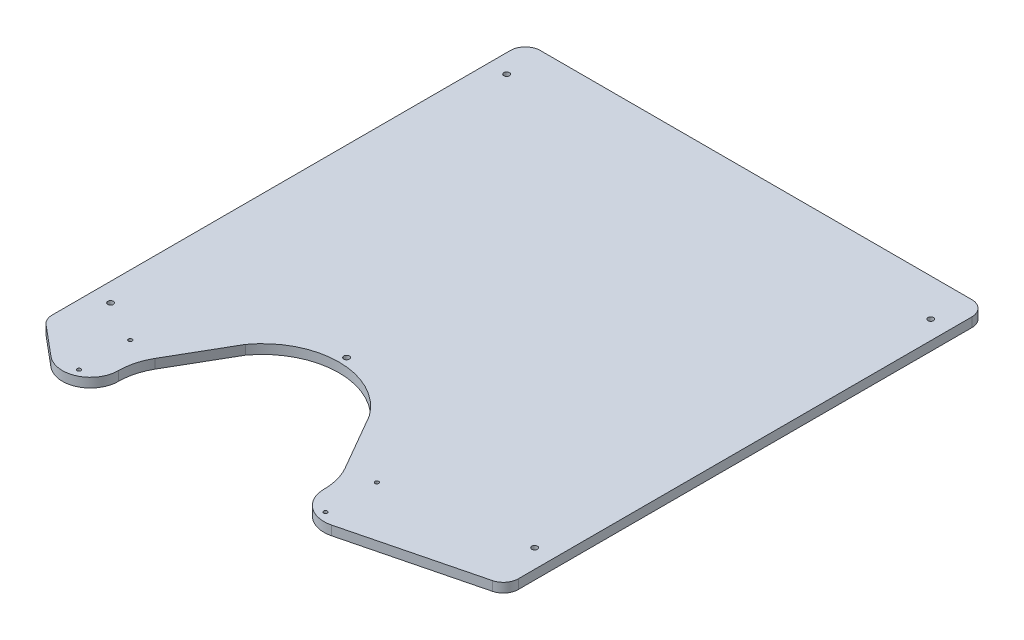
SolidWorks part; units mm, degrees
material "ABS PC"
ref_plane "Plan de face" through (0, 0, 0) normal (0, 0, 1) x (1, 0, 0)
ref_plane "Plan de dessus" through (0, 0, 0) normal (0, 1, 0) x (1, 0, 0)
ref_plane "Plan de droite" through (0, 0, 0) normal (1, 0, 0) x (0, 0, -1)
sketch "Esquisse1" plane through (0, 0, 0) normal (0, 1, 0) x (1, 0, 0)
  line L0 (-60.6815, -188.3301) -> (-75.8539, -214.6094) construction
  line L1 (-115.5, 31.2) -> (115.5, 31.2)
  line L2 (-123.5, 23.2) -> (-123.5, -222.0619)
  line L3 (-60.6815, -188.3301) -> (-75.8539, -214.6094)
  line L4 (123.5, 23.2) -> (123.5, -219.5635)
  line L5 (25.8539, -214.6094) -> (10.6815, -188.3301) construction
  line L6 (25.8539, -214.6094) -> (10.6815, -188.3301)
  line L7 (8.1815, -184) -> (10.6815, -188.3301)
  line L8 (-58.1815, -184) -> (-60.6815, -188.3301)
  line L9 (-120.6327, -228.1983) -> (-104.6238, -241.5886)
  line L10 (117.4519, -227.3217) -> (48.6599, -244.6295)
  line L12 (-108.5, -220.8) -> (-118.5, -220.8) construction
  line L15 (-118.5, -220.8) -> (-118.5, 31.2) construction
  line L16 (118.5, -220.8) -> (118.5, 31.2) construction
  line L18 (108.5, 31.2) -> (-108.5, 31.2) construction
  arc A0 (8.1815, -184) -> (-58.1815, -184) centre (-25, -208.0829) ccw construction
  arc A1 (8.1815, -184) -> (-58.1815, -184) centre (-25, -208.0829) ccw
  circle A2 centre (-91, -240.25) radius 1.95 construction
  arc A4 (30, -230.0829) -> (45, -245.0829) centre (45, -230.0829) ccw construction
  arc A5 (30, -230.0829) -> (25.8539, -214.6094) centre (-0.9469, -230.0829) ccw construction
  arc A6 (30, -230.0829) -> (25.8539, -214.6094) centre (-0.9469, -230.0829) ccw
  arc A7 (-95, -245.0829) -> (-80, -230.0829) centre (-95, -230.0829) ccw construction
  circle A8 centre (41, -212.75) radius 1
  circle A9 centre (41, -240.25) radius 1
  arc A10 (-115.5, 31.2) -> (-123.5, 23.2) centre (-115.5, 23.2) ccw
  arc A11 (115.5, 31.2) -> (123.5, 23.2) centre (115.5, 23.2) cw
  arc A12 (117.4519, -227.3217) -> (123.5, -219.5635) centre (115.5, -219.5635) ccw
  arc A13 (-123.5, -222.0619) -> (-120.6327, -228.1983) centre (-115.5, -222.0619) ccw
  arc A14 (-87.0138, -242.7801) -> (-80, -230.0829) centre (-95, -230.0829) ccw
  arc A15 (-75.8539, -214.6094) -> (-80, -230.0829) centre (-49.0531, -230.0829) ccw construction
  arc A16 (-75.8539, -214.6094) -> (-80, -230.0829) centre (-49.0531, -230.0829) ccw
  arc A17 (30, -230.0829) -> (42.3384, -244.8448) centre (45, -230.0829) ccw
  arc A18 (42.3384, -244.8448) -> (48.6599, -244.6295) centre (45, -230.0829) ccw
  arc A19 (-87.0138, -242.7801) -> (-104.6238, -241.5886) centre (-95, -230.0829) cw
  circle A20 centre (-91, -212.75) radius 1
  circle A21 centre (-91, -240.25) radius 1
  point P31 (-123.5, -225.8)
  point P44 (123.5, -225.8)
  dimension "D2" = 2
  dimension "D6" = 8
  dimension "D3" = 5
  dimension "D4" = 5
  dimension "D5" = 5
extrude "Boss.-Extru.1" add sketch "Esquisse1" against normal blind 5
sketch "Esquisse2" plane through (0, 0, 0) normal (0, 1, 0) x (1, 0, 0)
  circle A0 centre (-113.5, 11.2) radius 1.5
  circle A1 centre (-25, -163) radius 1.5
  circle A2 centre (113.5, 11.2) radius 1.5
  circle A3 centre (113.5, -200.8) radius 1.5
  circle A4 centre (-113.5, -200.8) radius 1.5
  dimension "D1" = 3
extrude "Enlèv. mat.-Extru.1" cut sketch "Esquisse2" against normal through all
